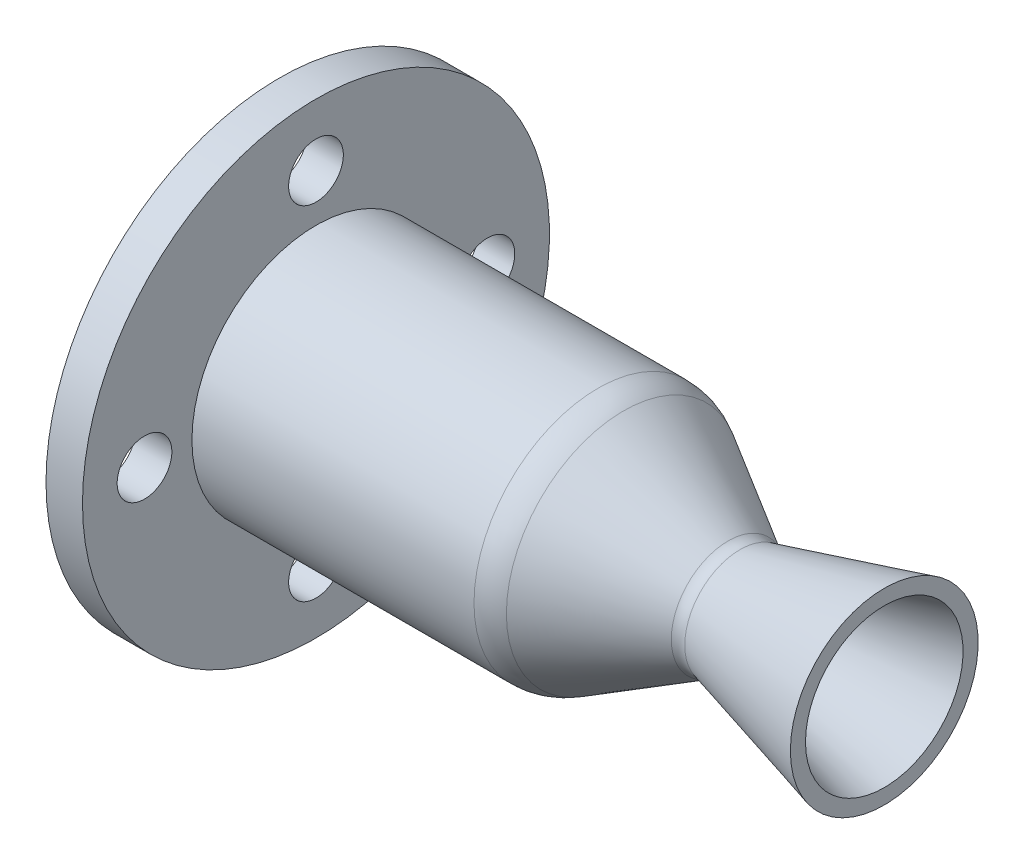
SolidWorks part; units mm, degrees
material "AISI 304"
ref_plane "Front Plane" through (0, 0, 0) normal (0, 0, 1) x (1, 0, 0)
ref_plane "Top Plane" through (0, 0, 0) normal (0, 1, 0) x (1, 0, 0)
ref_plane "Right Plane" through (0, 0, 0) normal (1, 0, 0) x (0, 0, -1)
sketch "Sketch1" plane through (0, 0, 0) normal (0, 0, 1) x (1, 0, 0)
  line L0 (0, 0) -> (366.3783, 0) construction
  line L1 (0, 0) -> (0, 38.1) construction
  line L2 (0, 38.1) -> (110.897, 38.1)
  line L3 (158.9188, 24.511) -> (158.9188, 13.97) construction
  line L4 (117.247, 36.3985) -> (153.6483, 15.3822)
  line L5 (150.9294, 13.97) -> (106.9103, 13.97) construction
  line L6 (161.647, 14.3292) -> (210.5452, 27.4314)
  line L7 (210.5452, 27.4314) -> (210.5452, 0) construction
  line L8 (12.7, 43.18) -> (110.897, 43.18)
  line L9 (119.787, 40.7979) -> (156.1883, 19.7816)
  line L10 (160.3322, 19.2361) -> (210.5452, 32.6906)
  line L11 (0, 43.18) -> (0, 38.1)
  line L12 (210.5452, 27.4314) -> (210.5452, 32.6906)
  line L13 (160.3322, 19.2361) -> (209.2304, 32.3383) construction
  line L14 (0, 43.18) -> (0, 81.28)
  line L15 (0, 81.28) -> (12.7, 81.28)
  line L16 (12.7, 81.28) -> (12.7, 43.18)
  line L17 (0, 43.18) -> (110.897, 43.18) construction
  arc A0 (153.6483, 15.3822) -> (161.647, 14.3292) centre (158.9188, 24.511) ccw
  arc A1 (110.897, 38.1) -> (117.247, 36.3985) centre (110.897, 25.4) cw
  arc A2 (110.897, 43.18) -> (119.787, 40.7979) centre (110.897, 25.4) cw
  arc A3 (156.1883, 19.7816) -> (160.3322, 19.2361) centre (158.9188, 24.511) ccw
  point P16 (114.3, 38.1)
  dimension "D4" = 21.082
  dimension "D9" = 12.7
  dimension "D1" = 38.1
  dimension "D2" = 114.3
  dimension "D5" = 30
  dimension "D6" = 15
  dimension "D7" = 27.4314
  dimension "D11" = 12.7
  dimension "D12" = 38.1
  dimension "D10" = 5.08
revolve "Revolve1" add sketch "Sketch1" angle 360 about L0
sketch "Sketch2" plane through (0, 0, 0) normal (-1, 0, 0) x (0, 0, 1)
  line L0 (-38.1, 0) -> (-81.28, 0) construction
  circle A0 centre (0, 0) radius 38.1 construction
  circle A1 centre (0, 0) radius 38.1 construction
  circle A2 centre (0, 0) radius 81.28 construction
  circle A3 centre (-59.69, 0) radius 9.525
  circle A4 centre (0, 59.69) radius 9.525
  circle A5 centre (59.69, 0) radius 9.525
  circle A6 centre (0, -59.69) radius 9.525
  point P22 (0, 0)
  dimension "D1" = 19.05
  dimension "D2" = 4
extrude "Cut-Extrude1" cut sketch "Sketch2" against normal through all
equation "\"l_star\"= .8m'characteristic length"
equation "\"R_t\"= .55in'throat radius"
equation "\"V_c\"= \"l_star\" * \"R_t\"'chamber volume"
equation "\"D_c\"= 3in'chamber diameter"
equation "\"L_c\"= \"V_c\" / ( ( pi * \"D_c\" ) / 4 )'chamber length"
equation "\"eps_x\"= 3.8557'expansion ratio"
equation "\"D_e\"= \"R_t\" * 2 * sqr ( \"eps_x\" )'exit diameter"
equation "\"arc_t\"= 1.5in * \"R_t\"'arc between convergent and divergent"
equation "\"D3@Sketch1\"=\"R_t\""
equation "\"D7@Sketch1\"=\"D_e\"/2"
equation "\"D1@Sketch1\"=\"D_c\"/2"
